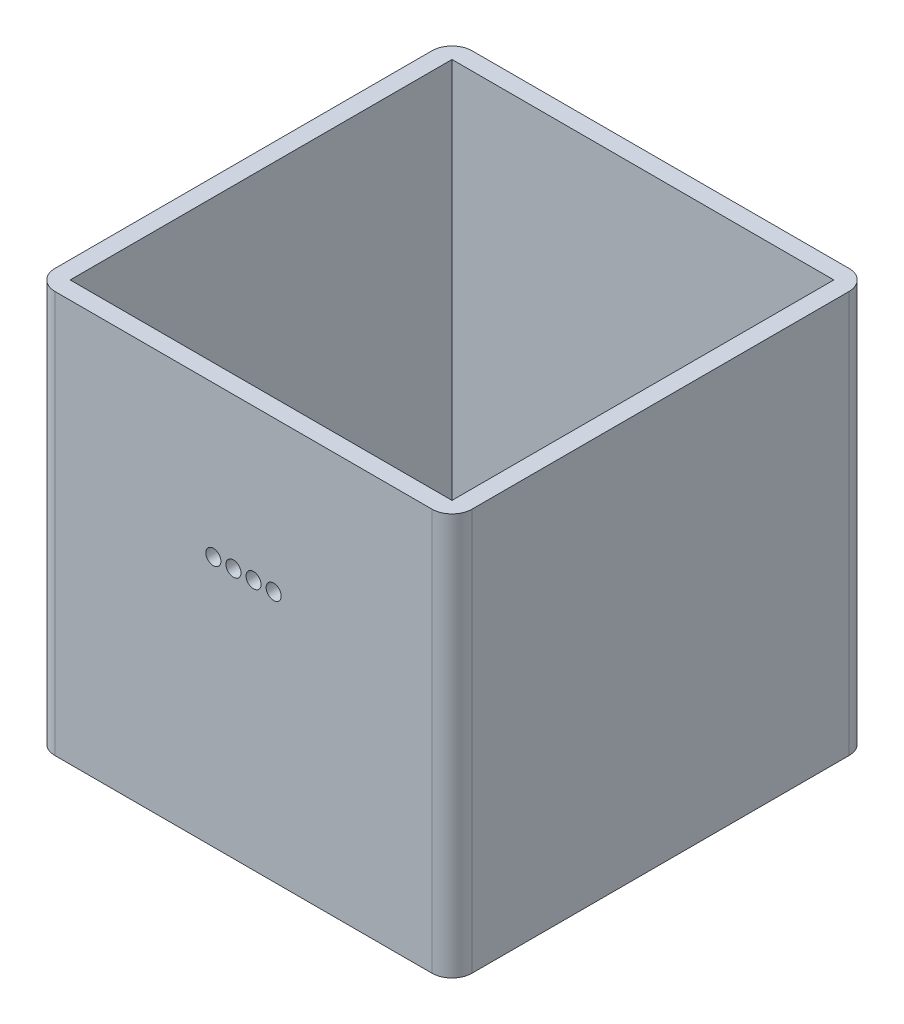
SolidWorks part; units mm, degrees
ref_plane "Front Plane" through (0, 0, 0) normal (0, 0, 1) x (1, 0, 0)
ref_plane "Top Plane" through (0, 0, 0) normal (0, 1, 0) x (1, 0, 0)
ref_plane "Right Plane" through (0, 0, 0) normal (1, 0, 0) x (0, 0, -1)
sketch "Sketch4" plane through (0, 0, 0) normal (0, 1, 0) x (1, 0, 0)
  line L1 (-41.5, 41.5) -> (41.5, 41.5)
  line L2 (-41.5, 41.5) -> (-41.5, -41.5)
  line L3 (-41.5, -41.5) -> (41.5, -41.5)
  line L4 (41.5, 41.5) -> (41.5, -41.5)
  point P4 (0, 0)
  point P5 (0, 0)
  point P6 (0, 0)
  point P7 (0, 0)
  point P8 (0, 0)
  point P9 (0, 0)
  point P10 (0, 0)
  point P11 (0, 0)
extrude "Boss-Extrude2" add sketch "Sketch4" along normal blind 40 and the other way blind 40
sketch "Sketch5" plane through (0, 0, 0) normal (0, 1, 0) x (1, 0, 0)
  line L1 (-38, 38) -> (38, 38)
  line L2 (-38, 38) -> (-38, -38)
  line L3 (-38, -38) -> (38, -38)
  line L4 (38, 38) -> (38, -38)
  point P4 (0, 0)
  point P5 (0, 0)
  point P6 (0, 0)
  point P7 (0, 0)
  point P8 (0, 0)
  point P9 (0, 0)
extrude "Cut-Extrude1" cut sketch "Sketch5" against normal blind 37.5 and the other way blind 50
sketch "Sketch6" plane through (0, 0, 0) normal (0, 0, 1) x (1, 0, 0)
  circle A0 centre (2, 10) radius 1.5
  circle A1 centre (6, 10) radius 1.5
  circle A2 centre (-2, 10) radius 1.5
  circle A3 centre (-6, 10) radius 1.5
extrude "Cut-Extrude2" cut sketch "Sketch6" along normal blind 74.5 and the other way blind 5
sketch "Sketch8" plane through (0, 0, 0) normal (0, 0, 1) x (1, 0, 0)
  line L0 (0, -41.25) -> (0, 41.25) construction
  circle A0 centre (0, -9) radius 1
  circle A1 centre (2.5, -9) radius 1
  circle A2 centre (0, -6.5) radius 1
  circle A3 centre (-2.5, -9) radius 1
  circle A4 centre (0, -11.5) radius 1
  point P4 (0, 0)
  point P11 (0, -8.3598)
  point P14 (0, 0)
  point P17 (0, 0)
  point P18 (0, 0)
  point P19 (0, 0)
  point P20 (0, 0)
  point P21 (0, 0)
  point P22 (0, 0)
  point P23 (0, 0)
extrude "Cut-Extrude3" cut sketch "Sketch8" against normal blind 70.5
sketch "Sketch9" plane through (0, 0, 0) normal (0, 0, 1) x (1, 0, 0)
  line L1 (18, -15) -> (30, -15)
  line L2 (18, -15) -> (18, -22)
  line L3 (18, -22) -> (30, -22)
  line L4 (30, -15) -> (30, -22)
  point P4 (0, 0)
  point P5 (0, 0)
  point P6 (0, 0)
  point P7 (0, 0)
  point P8 (0, 0)
  point P9 (0, 0)
extrude "Cut-Extrude4" cut sketch "Sketch9" against normal blind 108.5
fillet "Fillet2" radius 1 4 edges at (18, -22, -39.75) (30, -22, -39.75) (18, -15, -39.75) (30, -15, -39.75)
fillet "Fillet3" radius 4 4 edges at (-41.5, 0, 41.5) (41.5, 0, -41.5) (41.5, 0, 41.5) (-41.5, 0, -41.5)
